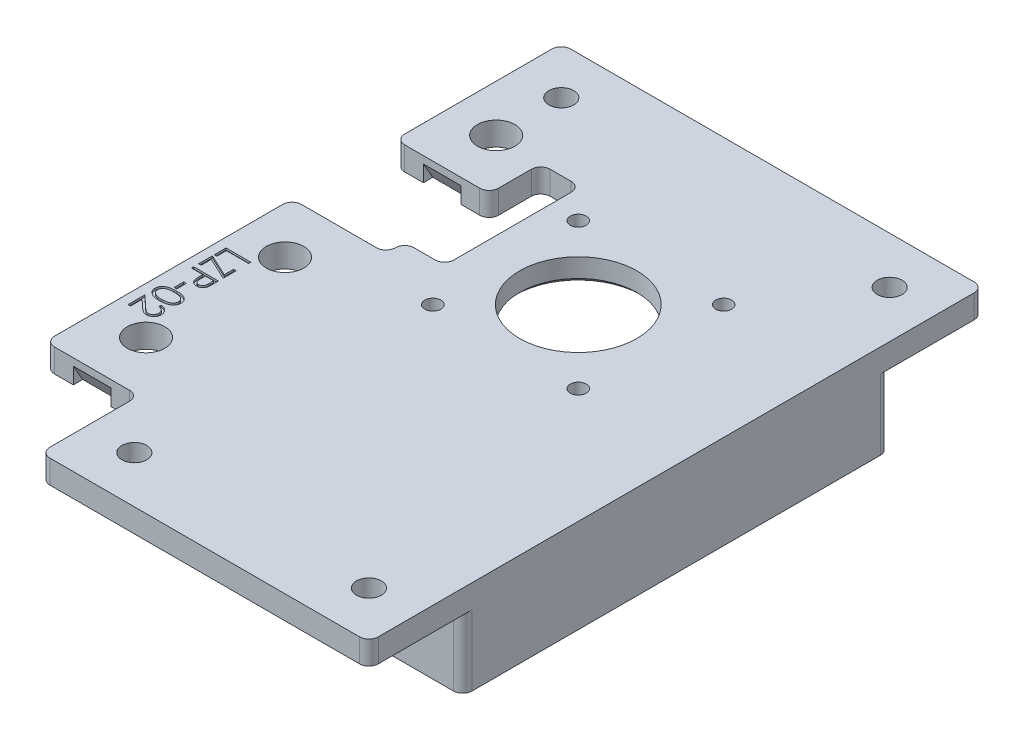
SolidWorks part; units mm, degrees
ref_plane "Front" through (0, 0, 0) normal (0, 0, 1) x (1, 0, 0)
ref_plane "Top" through (0, 0, 0) normal (0, 1, 0) x (1, 0, 0)
ref_plane "Right" through (0, 0, 0) normal (1, 0, 0) x (0, 0, -1)
sketch "Sketch1" plane through (0, 0, 0) normal (0, 1, 0) x (1, 0, 0)
  line L1 (0, 0) -> (90, 0)
  line L2 (0, 0) -> (0, 131)
  line L3 (0, 131) -> (90, 131)
  line L4 (90, 0) -> (90, 131)
  dimension "D1" = 90
  dimension "D2" = 131
extrude "Boss-Extrude1" add sketch "Sketch1" along normal blind 5
sketch "Sketch2" plane through (0, 5, 0) normal (0, 1, 0) x (1, 0, 0)
  line L0 (0, 94.625) -> (20, 94.625)
  line L1 (0, 131) -> (0, 0) construction
  line L2 (20, 94.625) -> (20, 91.625)
  line L3 (20, 91.625) -> (28.5, 91.625)
  line L4 (28.5, 91.625) -> (28.5, 77.625)
  line L5 (28.5, 77.625) -> (20, 77.625)
  line L6 (20, 77.625) -> (20, 74.625)
  line L7 (20, 74.625) -> (0, 74.625)
  line L8 (0, 74.625) -> (0, 94.625)
  line L10 (0, 0) -> (20, 0)
  line L11 (0, 0) -> (0, 20)
  line L12 (0, 20) -> (20, 20)
  line L13 (20, 0) -> (20, 20)
  line L15 (90, 131) -> (0, 131) construction
  line L28 (28.5, 106.125) -> (28.5, 91.625) construction
  line L29 (34.5, 69.125) -> (65.5, 69.125) construction
  line L30 (34.5, 69.125) -> (34.5, 100.125) construction
  line L31 (34.5, 100.125) -> (65.5, 100.125) construction
  line L32 (65.5, 69.125) -> (65.5, 100.125) construction
  line L33 (34.5, 69.125) -> (65.5, 100.125) construction
  line L34 (34.5, 100.125) -> (65.5, 69.125) construction
  line L35 (71.5, 63.125) -> (28.5, 63.125) construction
  line L36 (71.5, 63.125) -> (71.5, 106.125) construction
  line L37 (71.5, 106.125) -> (28.5, 106.125) construction
  line L38 (28.5, 63.125) -> (28.5, 106.125) construction
  line L39 (71.5, 63.125) -> (28.5, 106.125) construction
  line L40 (71.5, 106.125) -> (28.5, 63.125) construction
  line L41 (28.5, 77.625) -> (28.5, 63.125) construction
  line L48 (32, 59.625) -> (68, 59.625) construction
  line L49 (32, 59.625) -> (32, 109.625) construction
  line L50 (32, 109.625) -> (68, 109.625) construction
  line L51 (68, 59.625) -> (68, 109.625) construction
  line L52 (32, 59.625) -> (68, 109.625) construction
  line L53 (32, 109.625) -> (68, 59.625) construction
  circle A0 centre (50, 84.625) radius 12.5
  circle A2 centre (65.5, 100.125) radius 1.7
  circle A3 centre (34.5, 100.125) radius 1.7
  circle A4 centre (65.5, 69.125) radius 1.7
  circle A5 centre (34.5, 69.125) radius 1.7
  circle A10 centre (32, 109.625) radius 1.7 construction
  circle A11 centre (68, 109.625) radius 1.7 construction
  circle A12 centre (68, 59.625) radius 1.7 construction
  circle A13 centre (32, 59.625) radius 1.7 construction
  point P54 (50, 84.625)
  dimension "D5" = 25
  dimension "D9" = 3.4
  dimension "D12" = 3.4
  dimension "D1" = 20
  dimension "D2" = 14
  dimension "D4" = 36.375
  dimension "D6" = 50
  dimension "D7" = 46.375
  dimension "D8" = 31
  dimension "D10" = 50
  dimension "D11" = 36
  dimension "D3" = 43
extrude "Cut-Extrude1" cut sketch "Sketch2" against normal up to next
hole_wizard "M5 Clearance Hole1" positions "Sketch3" profile "Sketch4" hole size "M5" standard "ANSI Metric" end condition through all
sketch "Sketch3" plane through (0, 5, 0) normal (0, 1, 0) x (1, 0, 0)
  line L0 (10, 20) -> (10, 131) construction
  line L1 (20, 20) -> (0, 20) construction
  line L2 (90, 131) -> (0, 131) construction
  line L5 (20, 10) -> (142.2662, 10) construction
  line L6 (20, 0) -> (20, 20) construction
  line L10 (0, 121) -> (90, 121) construction
  line L11 (0, 131) -> (0, 94.625) construction
  line L12 (90, 0) -> (90, 131) construction
  line L14 (20, 0) -> (90, 0) construction
  line L15 (0, 74.625) -> (0, 20) construction
  line L16 (90, 0) -> (90, 131) construction
  line L17 (90, 111) -> (0, 111) construction
  line L18 (90, 0) -> (90, 131) construction
  line L19 (20, 131) -> (20, 20) construction
  point P31 (10, 121)
  point P37 (80, 121)
  point P42 (30, 10)
  point P45 (80, 10)
  dimension "D1" = 10
  dimension "D2" = 10
  dimension "D3" = 10
  dimension "D4" = 10
  dimension "D5" = 10
  dimension "D6" = 10
  dimension "D7" = 20
sketch "Sketch4" plane through (80, 5, -10) normal (1, 0, 0) x (0, 0, 1)
  line L0 (0, 0) -> (0, 5)
  line L1 (0, 5) -> (2.65, 5)
  line L2 (2.65, 5) -> (2.65, 0)
  line L5 (2.65, 0) -> (0, 0)
  line L11 (0, -6.35) -> (0, 107.95) construction
  dimension "Thru Hole Dia." = 5.3
  dimension "Thru Hole Depth" = 5
sketch "Sketch6" plane through (0, 0, 0) normal (0, -1, 0) x (-1, 0, 0)
  line L0 (-20, 20) -> (0, 20) construction
  line L1 (0, 74.625) -> (-20, 74.625) construction
  line L2 (0, 74.625) -> (0, 20) construction
  line L3 (-20, 94.625) -> (0, 94.625) construction
  line L4 (0, 131) -> (0, 94.625) construction
  circle A0 centre (-10, 32.5) radius 4
  circle A1 centre (-10, 62.125) radius 4
  circle A2 centre (-10, 107.125) radius 4
  dimension "D2" = 8
  dimension "D1" = 12.5
  dimension "D3" = 12.5
  dimension "D4" = 10
  dimension "D5" = 10
  dimension "D6" = 12.5
  dimension "D7" = 10
extrude "Cut-Extrude2" cut sketch "Sketch6" against normal blind 10
other "Move Face1" flip direction yes face at (10, 2.5, -20) face at (10, 2.5, -94.625) face at (10, 2.5, -74.625) offset 1 parameters "D1"=1
sketch "Sketch9" plane through (0, 0, 0) normal (0, -1, 0) x (1, 0, 0)
  line L0 (90, -111) -> (90, -20)
  line L1 (90, 0) -> (90, -131) construction
  line L2 (90, -20) -> (20, -20)
  line L3 (20, -20) -> (20, -73.625)
  line L4 (90, -111) -> (71, -111)
  line L5 (90, -131) -> (0, -131) construction
  line L6 (71, -111) -> (71, -106)
  line L7 (71, -106) -> (85, -106)
  line L8 (85, -106) -> (85, -25)
  line L9 (85, -25) -> (25, -25)
  line L10 (25, -25) -> (25, -73.625)
  line L11 (25, -73.625) -> (20, -73.625)
  line L12 (20, 0) -> (90, 0) construction
  line L13 (0, -73.625) -> (20, -73.625) construction
  line L14 (20, -73.625) -> (20, -77.625) construction
  dimension "D1" = 20
  dimension "D2" = 5
  dimension "D3" = 20
  dimension "D4" = 5
  dimension "D7" = 19
  dimension "D8" = 5
extrude "Boss-Extrude2" add sketch "Sketch9" along normal blind 15
fillet "Fillet4" radius 3 3 edges at (25, -7.5, -25) (85, -7.5, -25) (85, -7.5, -106)
fillet "Fillet5" radius 2 7 edges at (90, -7.5, -20) (90, -7.5, -111) (71, -7.5, -111) (71, -7.5, -106) (20, -7.5, -20) (25, -7.5, -73.625) (20, -7.5, -73.625)
ref_plane "Plane1" through (10, 0, 0) normal (-1, 0, 0) x (0, 0, 1)
sketch "Sketch10" plane through (10, 0, 0) normal (-1, 0, 0) x (0, 0, 1)
  line L0 (-73.625, 0) -> (-73.625, 3.4641)
  line L1 (-28, 0) -> (-103, 0) construction
  line L2 (-73.625, 0) -> (-73.625, 5) construction
  line L3 (-73.625, 3.4641) -> (-71.625, 0)
  line L5 (-71.625, 0) -> (-73.625, 0)
  line L6 (-97.625, 0) -> (-95.625, 0)
  line L8 (-95.625, 0) -> (-95.625, 3.4641)
  line L10 (-95.625, 3.4641) -> (-97.625, 0)
  line L11 (-21, 0) -> (-23, 0)
  line L12 (-22, 0) -> (-20, 0) construction
  line L13 (-22, 0) -> (-71.625, 0) construction
  line L16 (-21, 0) -> (-21, 3.4641)
  line L17 (-21, 0) -> (-21, 5) construction
  line L18 (-21, 3.4641) -> (-23, 0)
  line L21 (-95.625, 0) -> (-95.625, 5) construction
  dimension "D1" = 30
  dimension "D2" = 2
extrude "Cut-Extrude5" cut sketch "Sketch10" against normal blind 4 and the other way blind 4
sketch "Sketch11" plane through (0, 5, 0) normal (0, 1, 0) x (1, 0, 0)
  line L5 (28.5, 77.625) -> (28.5, 91.625) construction
  line L6 (20, 91.625) -> (28.5, 91.625)
  line L7 (20, 91.625) -> (20, 106.625)
  line L8 (20, 106.625) -> (28.5, 106.625)
  line L9 (28.5, 91.625) -> (28.5, 106.625)
  dimension "D1" = 15
extrude "Cut-Extrude6" cut sketch "Sketch11" against normal through all
fillet "Fillet6" radius 2 14 edges at (28.5, 2.5, -77.625) (90, 2.5, 0) (90, 2.5, -131) (0, 2.5, -131) (0, 2.5, -95.625) (20, 2.5, -73.625) (20, 2.5, -77.625) (0, 2.5, -73.625) (0, 2.5, -21) (20, 2.5, 0) (20, 2.5, -21) (28.5, 2.5, -106.625) (20, 2.5, -95.625) (20, 2.5, -106.625)
chamfer "Chamfer1" distance 1 angle 45 1 edges at (50, 0, -97.125)
mirror "Mirror1" [suppressed] of bodies 111 108
delete or keep bodies "Body-Delete/Keep 1" [suppressed] type delete bodies bodies 111
sketch "Sketch12" plane through (0, 5, 0) normal (0, 1, 0) x (1, 0, 0)
  line L0 (2, 73.625) -> (2, 21) construction
  line L1 (2, 73.625) -> (18, 73.625) construction
  line L2 (18, 21) -> (2, 21) construction
  line L3 (0, 71.625) -> (0, 23) construction
  text T0 "LZP-02" font "Century Gothic" height in points 20
  dimension "D1" = 2
extrude "Cut-Extrude7" cut sketch "Sketch12" against normal blind 0.4
sketch "Sketch13" [suppressed] plane through (0, 5, 0) normal (0, 1, 0) x (1, 0, 0)
  line L0 (178, 21) -> (178, 73.625) construction
  line L1 (178, 73.625) -> (162, 73.625) construction
  line L2 (162, 21) -> (178, 21) construction
  line L3 (180, 71.625) -> (180, 23) construction
  text T0 "RZP-02" font "Century Gothic" height in points 20
  dimension "D1" = 2
extrude "Cut-Extrude8" [suppressed] cut sketch "Sketch13" against normal blind 0.4
equation "\"D4@Sketch2\"=\"D7@Sketch2\"-10"
equation "\"D3@Sketch6\"=\"D1@Sketch6\""
equation "\"D6@Sketch6\"=\"D1@Sketch6\""
equation "\"D8@Sketch9\"=\"D4@Sketch9\""
equation "\"D2@Sketch9\"=\"D4@Sketch9\""
